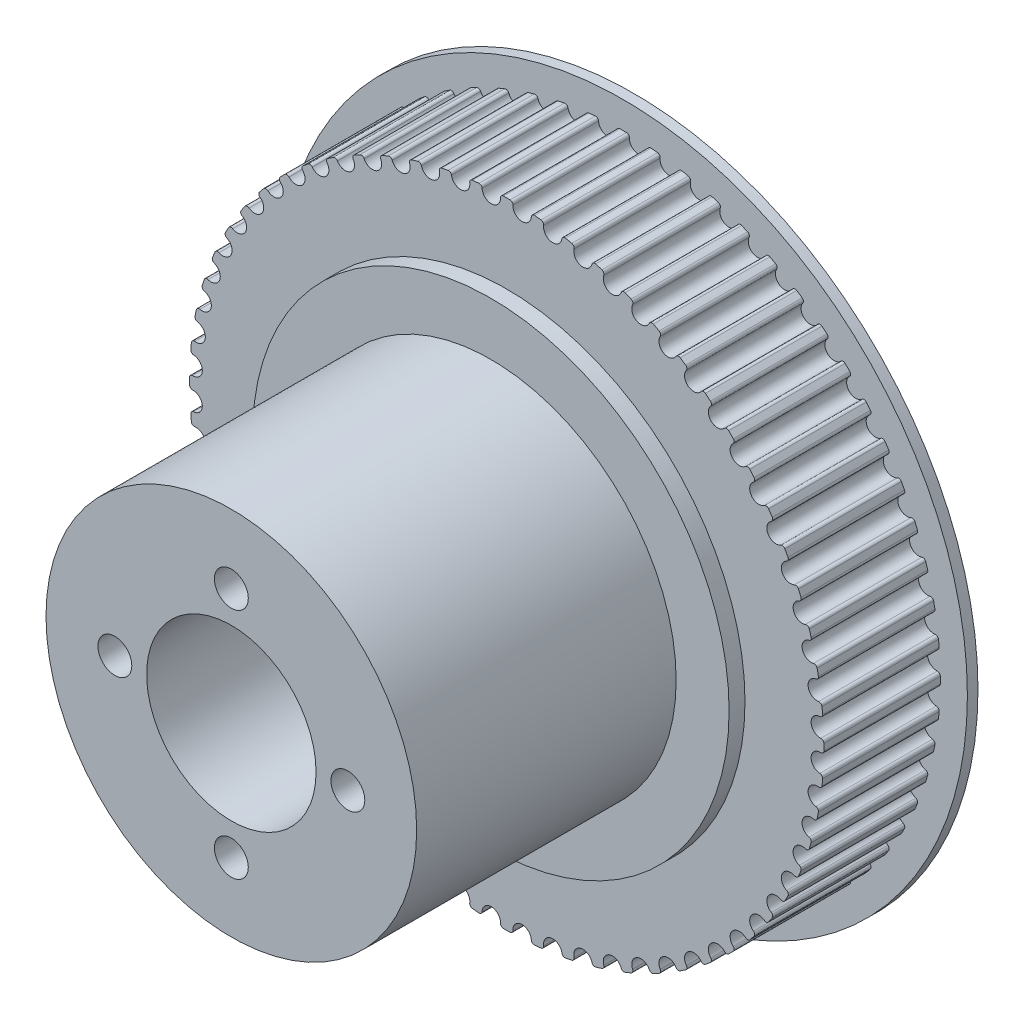
SolidWorks part; units mm, degrees
ref_plane "Front Plane" through (0, 0, 0) normal (1, 0, 0) x (0, 1, 0)
ref_plane "Top Plane" through (0, 0, 0) normal (0, 0, 1) x (0, 1, 0)
ref_plane "Right Plane" through (0, 0, 0) normal (0, 1, 0) x (-1, 0, 0)
sketch "Sketch1" plane through (0, 0, 0) normal (0, 0, 1) x (0, 1, 0)
  line L0 (0, 0) -> (0, 29.9477)
  line L2 (0, 0) -> (1.4121, 28.7431) construction
  line L3 (1.4121, 28.7431) -> (1.4547, 29.612) construction
  line L4 (0, 0) -> (2.9354, 29.8035)
  circle A0 centre (0, 0) radius 32.5
  arc A1 (0, 29.9477) -> (0.6492, 29.9407) centre (0, 0) cw
  arc A2 (0.6492, 29.9407) -> (2.2886, 29.8602) centre (1.4547, 29.612) ccw
  arc A4 (2.9354, 29.8035) -> (2.2886, 29.8602) centre (0, 0) ccw
  dimension "D1" = 65
  dimension "D2" = 29.9477
  dimension "D6" = 2.813
  dimension "D3" = 0.87
  dimension "D4" = 28.7777
extrude "Boss-Extrude2" add sketch "Sketch1" along normal blind 11 from offset 1
fillet "Fillet1" radius 0.28 2 edges at (-29.9407, 0.6492, 6.5) (-29.8602, 2.2886, 6.5)
pattern_circular "CirPattern4" count 64 over 360 about axis through (0, 0, 12) along (0, 0, -1) of "Fillet1", "Boss-Extrude2" reverse direction yes
extrude "Boss-Extrude3" add sketch "Sketch1<4>" along normal blind 1 contours A0
sketch "Sketch1<4>" plane through (0, 0, 0) normal (0, 0, 1) x (0, 1, 0) same geometry as "Sketch1"
sketch "Sketch2" plane through (0, 0, 12) normal (0, 0, 1) x (1, 0, 0)
  line L0 (-8.25, 2.75) -> (-8.25, -2.75)
  line L1 (-2.75, -8.25) -> (2.75, -8.25)
  line L2 (-2.75, -8.25) -> (-2.75, -13.75)
  line L3 (-2.75, -13.75) -> (2.75, -13.75)
  line L4 (2.75, -8.25) -> (2.75, -13.75)
  line L5 (-2.75, -8.25) -> (2.75, -13.75) construction
  line L6 (-2.75, -13.75) -> (2.75, -8.25) construction
  line L7 (-8.25, 2.75) -> (-13.75, 2.75)
  line L8 (-13.75, 2.75) -> (-13.75, -2.75)
  line L9 (-8.25, -2.75) -> (-13.75, -2.75)
  line L10 (-8.25, 2.75) -> (-13.75, -2.75) construction
  line L11 (-13.75, 2.75) -> (-8.25, -2.75) construction
  line L12 (2.75, 8.25) -> (-2.75, 8.25)
  line L13 (2.75, 8.25) -> (2.75, 13.75)
  line L14 (2.75, 13.75) -> (-2.75, 13.75)
  line L15 (-2.75, 8.25) -> (-2.75, 13.75)
  line L16 (2.75, 8.25) -> (-2.75, 13.75) construction
  line L17 (2.75, 13.75) -> (-2.75, 8.25) construction
  line L18 (8.25, -2.75) -> (8.25, 2.75)
  line L19 (8.25, -2.75) -> (13.75, -2.75)
  line L20 (13.75, -2.75) -> (13.75, 2.75)
  line L21 (8.25, 2.75) -> (13.75, 2.75)
  line L22 (8.25, -2.75) -> (13.75, 2.75) construction
  line L23 (13.75, -2.75) -> (8.25, 2.75) construction
  circle A0 centre (0, 0) radius 22.5
  circle A1 centre (0, 0) radius 17.5
  circle A2 centre (0, 0) radius 8
  circle A3 centre (0, 0) radius 11 construction
  circle A4 centre (0, -11) radius 1.6
  circle A5 centre (-11, 0) radius 1.6
  circle A6 centre (0, 11) radius 1.6
  circle A7 centre (11, 0) radius 1.6
  dimension "D1" = 45
  dimension "D2" = 35
  dimension "D3" = 16
  dimension "D4" = 22
  dimension "D5" = 3.2
  dimension "D6" = 5.5
  dimension "D7" = 4
extrude "Boss-Extrude4" add sketch "Sketch2" along normal blind 1.5 contours A0
extrude "Boss-Extrude5" add sketch "Sketch2<3>" along normal blind 24.5 from surface contours A1 starting at face at (22.5, 0, 13.5)
sketch "Sketch2<3>" plane through (0, 0, 12) normal (0, 0, 1) x (1, 0, 0) same geometry as "Sketch2"
extrude "Cut-Extrude1" cut sketch "Sketch2<5>" against normal through all both and the other way through all contours A5 | A6 | A4 | A7 | A2
sketch "Sketch2<5>" plane through (0, 0, 12) normal (0, 0, 1) x (1, 0, 0) same geometry as "Sketch2"
extrude "Cut-Extrude2" cut sketch "Sketch2<6>" along normal blind 9 from surface contours L3 L4 L1 L2 | L19 L20 L21 L18 | L12 L15 L14 L13 | L9 L8 L7 L0 starting at face at (-9.4, 0, 0)
sketch "Sketch2<6>" plane through (0, 0, 12) normal (0, 0, 1) x (1, 0, 0) same geometry as "Sketch2"
equation "\"Teeth\"= 64"
equation "\"D4@Sketch1\"=\"D2@Sketch1\"-1.17"
equation "\"D2@Sketch1\"=\"Teeth\" * 3 / 2 / PI - 0.61"
equation "\"D1@CirPattern4\"=\"Teeth\""
